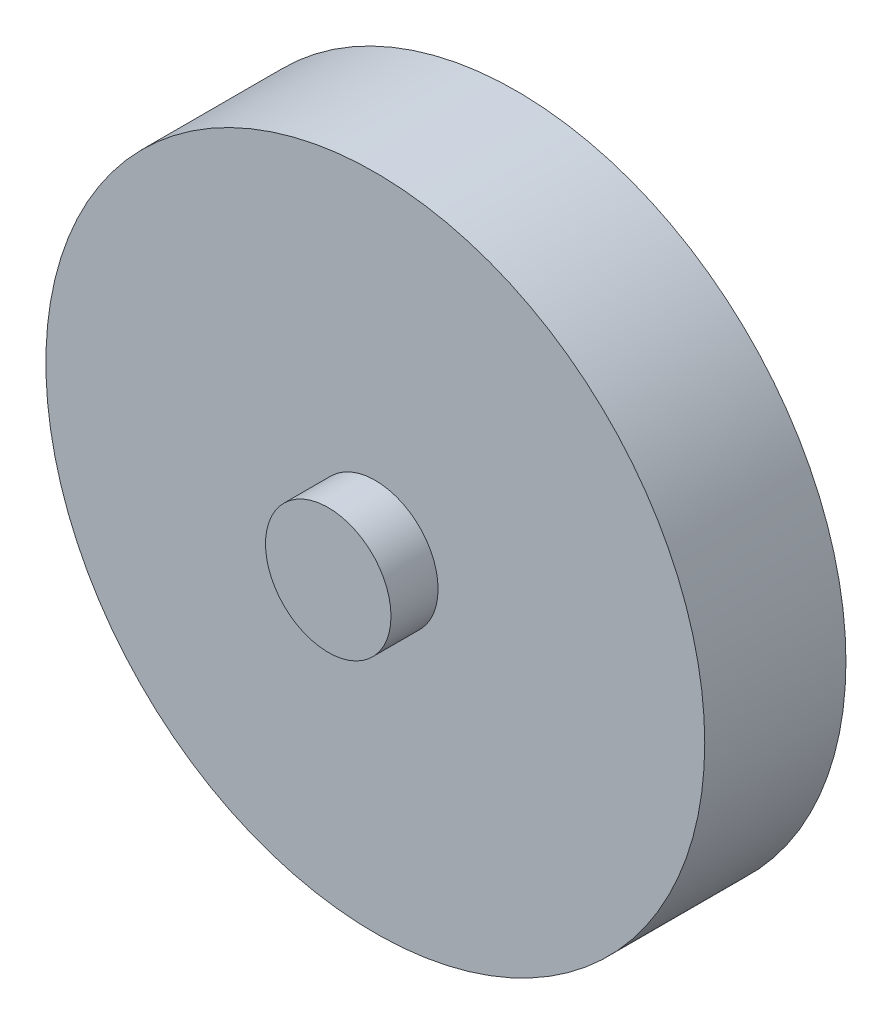
SolidWorks part; units mm, degrees
ref_plane "前视基准面" through (0, 0, 0) normal (0, 0, 1) x (1, 0, 0)
ref_plane "上视基准面" through (0, 0, 0) normal (0, 1, 0) x (1, 0, 0)
ref_plane "右视基准面" through (0, 0, 0) normal (1, 0, 0) x (0, 0, -1)
other "Configuration Table"
sketch "草图1" plane through (0, 0, 0) normal (0, 0, 1) x (1, 0, 0)
  circle A0 centre (0, 0) radius 8
extrude "凸台-拉伸1" add sketch "草图1" along normal blind 24
sketch "草图2" plane through (0, 0, 0) normal (0, 0, 1) x (1, 0, 0)
  circle A0 centre (0, 0) radius 42
extrude "凸台-拉伸2" add sketch "草图2" along normal blind 18
sketch "草图3" plane through (0, 0, 18) normal (0, 0, 1) x (1, 0, 0)
  line L0 (37.3016, 3.8521) -> (37.3889, 3.8612)
  line L1 (37.3889, 3.8612) -> (37.4611, 3.8717)
  line L2 (37.4611, 3.8717) -> (37.6757, 3.9151)
  line L3 (37.6757, 3.9151) -> (38.0282, 4.0092)
  line L4 (38.0282, 4.0092) -> (38.5127, 4.1711)
  line L5 (38.5127, 4.1711) -> (39.1215, 4.4175)
  line L6 (39.1215, 4.4175) -> (39.8456, 4.7642)
  line L7 (39.8456, 4.7642) -> (40.6741, 4.7642)
  line L8 (40.6741, 4.7642) -> (41.5951, 5.8179)
  line L9 (41.5951, 5.8179) -> (41.5951, 4.7642)
  line L10 (41.5951, 4.7642) -> (41.8082, 4.0092)
  line L11 (41.8082, 4.0092) -> (41.951, 2.0289)
  line L12 (41.951, 2.0289) -> (42, 0)
  line L13 (42, 0) -> (40.6741, 1.2633)
  line L14 (40.6741, 1.2633) -> (40.1003, 1.5277)
  line L15 (40.1003, 1.5277) -> (39.3309, 1.7569)
  line L16 (39.3309, 1.7569) -> (38.6911, 1.905)
  line L17 (38.6911, 1.905) -> (38.1872, 1.9891)
  line L18 (38.1872, 1.9891) -> (37.8243, 2.0269)
  line L19 (37.8243, 2.0269) -> (37.6055, 2.0362)
  line L20 (37.6055, 2.0362) -> (37.5326, 2.0353)
  line L21 (37.5326, 2.0353) -> (37.445, 2.0305)
  line L22 (37.445, 2.0305) -> (37.4175, 2.4866)
  line L23 (37.4175, 2.4866) -> (37.3844, 2.9422)
  line L24 (37.3844, 2.9422) -> (37.3458, 3.3974)
  line L25 (37.3458, 3.3974) -> (37.3016, 3.8521)
  line L26 (36.2398, 9.64) -> (36.3245, 9.6625)
  line L27 (36.3245, 9.6625) -> (36.3942, 9.6842)
  line L28 (36.3942, 9.6842) -> (36.5993, 9.7607)
  line L29 (36.5993, 9.7607) -> (36.9328, 9.9088)
  line L30 (36.9328, 9.9088) -> (37.386, 10.1445)
  line L31 (37.386, 10.1445) -> (37.9488, 10.483)
  line L32 (37.9488, 10.483) -> (38.6097, 10.9387)
  line L33 (38.6097, 10.9387) -> (39.3558, 11.5248)
  line L34 (39.3558, 11.5248) -> (39.8456, 11.5248)
  line L35 (39.8456, 11.5248) -> (40.5247, 11.034)
  line L36 (40.5247, 11.034) -> (40.5247, 10.483)
  line L37 (40.5247, 10.483) -> (41.1171, 8.5665)
  line L38 (41.1171, 8.5665) -> (41.3571, 7.3204)
  line L39 (41.3571, 7.3204) -> (39.8456, 7.3204)
  line L40 (39.8456, 7.3204) -> (39.3676, 7.782)
  line L41 (39.3676, 7.782) -> (37.9488, 7.782)
  line L42 (37.9488, 7.782) -> (37.9167, 7.9341)
  line L43 (37.9167, 7.9341) -> (37.4059, 7.9384)
  line L44 (37.4059, 7.9384) -> (37.0415, 7.9189)
  line L45 (37.0415, 7.9189) -> (36.824, 7.8939)
  line L46 (36.824, 7.8939) -> (36.7521, 7.8816)
  line L47 (36.7521, 7.8816) -> (36.6663, 7.8632)
  line L48 (36.6663, 7.8632) -> (36.5678, 8.3093)
  line L49 (36.5678, 8.3093) -> (36.4639, 8.7542)
  line L50 (36.4639, 8.7542) -> (36.2398, 9.64)
  line L51 (34.2856, 15.1904) -> (34.3658, 15.226)
  line L52 (34.3658, 15.226) -> (34.4312, 15.2583)
  line L53 (34.4312, 15.2583) -> (34.6218, 15.3659)
  line L54 (34.6218, 15.3659) -> (34.9281, 15.5643)
  line L55 (34.9281, 15.5643) -> (35.3388, 15.868)
  line L56 (35.3388, 15.868) -> (35.8417, 16.2905)
  line L57 (35.8417, 16.2905) -> (36.4232, 16.8439)
  line L58 (36.4232, 16.8439) -> (37.0683, 17.5395)
  line L59 (37.0683, 17.5395) -> (37.7615, 18.3868)
  line L60 (37.7615, 18.3868) -> (37.7615, 17.5395)
  line L61 (37.7615, 17.5395) -> (38.8029, 16.0727)
  line L62 (38.8029, 16.0727) -> (39.0096, 15.5643)
  line L63 (39.0096, 15.5643) -> (39.7028, 13.7)
  line L64 (39.7028, 13.7) -> (39.0096, 13.7)
  line L65 (39.0096, 13.7) -> (37.9488, 13.7)
  line L66 (37.9488, 13.7) -> (36.4232, 13.7)
  line L67 (36.4232, 13.7) -> (36.2087, 13.7679)
  line L68 (36.2087, 13.7679) -> (35.7035, 13.6922)
  line L69 (35.7035, 13.6922) -> (35.3467, 13.616)
  line L70 (35.3467, 13.616) -> (35.1358, 13.5573)
  line L71 (35.1358, 13.5573) -> (35.0666, 13.5339)
  line L72 (35.0666, 13.5339) -> (34.9848, 13.5023)
  line L73 (34.9848, 13.5023) -> (34.8177, 13.9275)
  line L74 (34.8177, 13.9275) -> (34.6455, 14.3506)
  line L75 (34.6455, 14.3506) -> (34.4681, 14.7716)
  line L76 (34.4681, 14.7716) -> (34.2856, 15.1904)
  line L77 (31.4872, 20.3669) -> (31.5608, 20.4145)
  line L78 (31.5608, 20.4145) -> (31.6204, 20.4566)
  line L79 (31.6204, 20.4566) -> (31.7918, 20.5928)
  line L80 (31.7918, 20.5928) -> (32.0632, 20.8367)
  line L81 (32.0632, 20.8367) -> (32.4214, 21.2009)
  line L82 (32.4214, 21.2009) -> (32.8521, 21.6968)
  line L83 (32.8521, 21.6968) -> (33.3398, 22.3344)
  line L84 (33.3398, 22.3344) -> (33.3398, 23.1223)
  line L85 (33.3398, 23.1223) -> (34.4202, 24.0676)
  line L86 (34.4202, 24.0676) -> (34.4202, 22.3344)
  line L87 (34.4202, 22.3344) -> (36.4232, 22.3344)
  line L88 (36.4232, 22.3344) -> (36.4232, 20.913)
  line L89 (36.4232, 20.913) -> (37.0708, 19.7422)
  line L90 (37.0708, 19.7422) -> (36.4232, 19.7422)
  line L91 (36.4232, 19.7422) -> (34.4202, 19.7422)
  line L92 (34.4202, 19.7422) -> (34.2465, 19.4213)
  line L93 (34.2465, 19.4213) -> (33.6091, 19.2627)
  line L94 (33.6091, 19.2627) -> (33.122, 19.1089)
  line L95 (33.122, 19.1089) -> (32.7815, 18.9778)
  line L96 (32.7815, 18.9778) -> (32.5824, 18.8868)
  line L97 (32.5824, 18.8868) -> (32.5178, 18.8529)
  line L98 (32.5178, 18.8529) -> (32.4419, 18.8089)
  line L99 (32.4419, 18.8089) -> (32.2103, 19.2027)
  line L100 (32.2103, 19.2027) -> (31.974, 19.5937)
  line L101 (31.974, 19.5937) -> (31.4872, 20.3669)
  line L102 (27.9134, 25.0418) -> (27.9787, 25.1004)
  line L103 (27.9787, 25.1004) -> (28.0309, 25.1513)
  line L104 (28.0309, 25.1513) -> (28.179, 25.3126)
  line L105 (28.179, 25.3126) -> (28.4089, 25.5959)
  line L106 (28.4089, 25.5959) -> (28.7057, 26.0117)
  line L107 (28.7057, 26.0117) -> (29.0535, 26.5689)
  line L108 (29.0535, 26.5689) -> (29.4354, 27.2749)
  line L109 (29.4354, 27.2749) -> (29.4354, 28.1358)
  line L110 (29.4354, 28.1358) -> (30.2315, 29.1558)
  line L111 (30.2315, 29.1558) -> (31.183, 28.1358)
  line L112 (31.183, 28.1358) -> (31.9387, 27.2749)
  line L113 (31.9387, 27.2749) -> (32.5284, 26.5689)
  line L114 (32.5284, 26.5689) -> (33.3398, 25.5433)
  line L115 (33.3398, 25.5433) -> (32.5284, 25.5433)
  line L116 (32.5284, 25.5433) -> (31.9387, 25.5433)
  line L117 (31.9387, 25.5433) -> (31.183, 25.3126)
  line L118 (31.183, 25.3126) -> (29.4354, 25.0418)
  line L119 (29.4354, 25.0418) -> (29.4354, 24.0676)
  line L120 (29.4354, 24.0676) -> (29.4091, 23.8723)
  line L121 (29.4091, 23.8723) -> (29.2267, 23.7513)
  line L122 (29.2267, 23.7513) -> (29.1682, 23.7077)
  line L123 (29.1682, 23.7077) -> (29.1001, 23.6524)
  line L124 (29.1001, 23.6524) -> (28.8098, 24.0051)
  line L125 (28.8098, 24.0051) -> (28.5152, 24.3543)
  line L126 (28.5152, 24.3543) -> (28.2164, 24.6999)
  line L127 (28.2164, 24.6999) -> (27.9134, 25.0418)
  line L128 (23.6524, 29.1558) -> (23.7077, 29.1558)
  line L129 (23.7077, 29.1558) -> (23.7513, 29.2267)
  line L130 (23.7513, 29.2267) -> (23.8723, 29.4091)
  line L131 (23.8723, 29.4091) -> (24.0551, 29.7249)
  line L132 (24.0551, 29.7249) -> (24.2832, 30.182)
  line L133 (24.2832, 30.182) -> (24.5395, 30.7867)
  line L134 (24.5395, 30.7867) -> (24.8063, 31.5438)
  line L135 (24.8063, 31.5438) -> (24.8063, 32.4565)
  line L136 (24.8063, 32.4565) -> (24.8063, 33.8917)
  line L137 (24.8063, 33.8917) -> (26.1255, 32.5725)
  line L138 (26.1255, 32.5725) -> (27.2768, 31.9371)
  line L139 (27.2768, 31.9371) -> (28.7057, 30.6591)
  line L140 (28.7057, 30.6591) -> (29.1558, 30.2315)
  line L141 (29.1558, 30.2315) -> (28.7057, 30.2315)
  line L142 (28.7057, 30.2315) -> (27.2768, 28.8026)
  line L143 (27.2768, 28.8026) -> (26.5689, 29.0535)
  line L144 (26.5689, 29.0535) -> (26.0117, 28.7057)
  line L145 (26.0117, 28.7057) -> (25.5959, 28.4089)
  line L146 (25.5959, 28.4089) -> (25.3126, 28.179)
  line L147 (25.3126, 28.179) -> (25.1513, 28.0309)
  line L148 (25.1513, 28.0309) -> (25.1004, 27.9787)
  line L149 (25.1004, 27.9787) -> (25.0418, 27.9134)
  line L150 (25.0418, 27.9134) -> (24.6999, 28.2164)
  line L151 (24.6999, 28.2164) -> (24.3543, 28.5152)
  line L152 (24.3543, 28.5152) -> (23.7077, 29.1558)
  line L153 (23.7077, 29.1558) -> (23.6524, 29.1558)
  line L154 (18.8089, 32.4565) -> (18.8529, 32.4565)
  line L155 (18.8529, 32.4565) -> (18.8868, 32.5824)
  line L156 (18.8868, 32.5824) -> (18.9778, 32.7815)
  line L157 (18.9778, 32.7815) -> (19.1089, 33.122)
  line L158 (19.1089, 33.122) -> (19.2627, 33.6091)
  line L159 (19.2627, 33.6091) -> (19.4213, 34.2465)
  line L160 (19.4213, 34.2465) -> (19.4213, 35.036)
  line L161 (19.4213, 35.036) -> (19.4213, 35.978)
  line L162 (19.4213, 35.978) -> (19.4213, 37.24)
  line L163 (19.4213, 37.24) -> (20.6833, 35.978)
  line L164 (20.6833, 35.978) -> (21.6699, 35.978)
  line L165 (21.6699, 35.978) -> (23.7513, 35.036)
  line L166 (23.7513, 35.036) -> (24.0676, 34.4202)
  line L167 (24.0676, 34.4202) -> (23.7513, 34.4202)
  line L168 (23.7513, 34.4202) -> (22.5026, 33.1715)
  line L169 (22.5026, 33.1715) -> (21.6699, 33.1715)
  line L170 (21.6699, 33.1715) -> (21.2009, 32.4214)
  line L171 (21.2009, 32.4214) -> (20.8367, 32.0632)
  line L172 (20.8367, 32.0632) -> (20.5928, 31.7918)
  line L173 (20.5928, 31.7918) -> (20.4566, 31.6204)
  line L174 (20.4566, 31.6204) -> (20.4145, 31.5608)
  line L175 (20.4145, 31.5608) -> (20.3669, 31.4872)
  line L176 (20.3669, 31.4872) -> (19.9818, 31.7329)
  line L177 (19.9818, 31.7329) -> (19.5937, 31.974)
  line L178 (19.5937, 31.974) -> (18.8529, 32.4565)
  line L179 (18.8529, 32.4565) -> (18.8089, 32.4565)
  line L180 (13.5023, 34.2465) -> (13.5339, 35.036)
  line L181 (13.5339, 35.036) -> (13.5573, 35.1358)
  line L182 (13.5573, 35.1358) -> (13.616, 35.3467)
  line L183 (13.616, 35.3467) -> (13.6922, 35.7035)
  line L184 (13.6922, 35.7035) -> (13.7679, 36.2087)
  line L185 (13.7679, 36.2087) -> (13.8248, 36.863)
  line L186 (13.8248, 36.863) -> (13.8248, 37.24)
  line L187 (13.8248, 37.24) -> (13.8248, 38.6136)
  line L188 (13.8248, 38.6136) -> (13.8248, 39.6595)
  line L189 (13.8248, 39.6595) -> (14.8931, 39.2708)
  line L190 (14.8931, 39.2708) -> (16.0727, 39.2708)
  line L191 (16.0727, 39.2708) -> (17.2376, 38.2997)
  line L192 (17.2376, 38.2997) -> (18.3868, 37.7615)
  line L193 (18.3868, 37.7615) -> (17.2376, 37.7615)
  line L194 (17.2376, 37.7615) -> (17.2376, 35.978)
  line L195 (17.2376, 35.978) -> (16.0727, 35.978)
  line L196 (16.0727, 35.978) -> (15.868, 35.3388)
  line L197 (15.868, 35.3388) -> (15.5643, 34.9281)
  line L198 (15.5643, 34.9281) -> (15.3659, 34.6218)
  line L199 (15.3659, 34.6218) -> (15.2583, 34.4312)
  line L200 (15.2583, 34.4312) -> (15.226, 34.3658)
  line L201 (15.226, 34.3658) -> (15.1904, 34.2856)
  line L202 (15.1904, 34.2856) -> (14.7716, 34.4681)
  line L203 (14.7716, 34.4681) -> (14.3506, 34.6455)
  line L204 (14.3506, 34.6455) -> (13.5339, 35.036)
  line L205 (13.5339, 35.036) -> (13.5023, 34.9848)
  line L206 (7.8632, 36.2087) -> (7.8816, 36.2087)
  line L207 (7.8816, 36.2087) -> (7.8939, 36.824)
  line L208 (7.8939, 36.824) -> (7.9189, 37.0415)
  line L209 (7.9189, 37.0415) -> (7.9384, 37.4059)
  line L210 (7.9384, 37.4059) -> (7.9341, 37.9167)
  line L211 (7.9341, 37.9167) -> (7.888, 38.5719)
  line L212 (7.888, 38.5719) -> (7.888, 38.6136)
  line L213 (7.888, 38.6136) -> (7.888, 39.6595)
  line L214 (7.888, 39.6595) -> (7.888, 41.2526)
  line L215 (7.888, 41.2526) -> (8.5665, 41.1171)
  line L216 (8.5665, 41.1171) -> (9.8047, 41.1171)
  line L217 (9.8047, 41.1171) -> (11.034, 41.1171)
  line L218 (11.034, 41.1171) -> (12.2532, 40.1729)
  line L219 (12.2532, 40.1729) -> (12.2532, 38.6136)
  line L220 (12.2532, 38.6136) -> (11.034, 38.6136)
  line L221 (11.034, 38.6136) -> (10.483, 37.9488)
  line L222 (10.483, 37.9488) -> (10.1445, 37.386)
  line L223 (10.1445, 37.386) -> (9.9088, 36.9328)
  line L224 (9.9088, 36.9328) -> (9.7607, 36.5993)
  line L225 (9.7607, 36.5993) -> (9.6842, 36.3942)
  line L226 (9.6842, 36.3942) -> (9.6625, 36.3245)
  line L227 (9.6625, 36.3245) -> (9.64, 36.2398)
  line L228 (9.64, 36.2398) -> (9.1978, 36.3545)
  line L229 (9.1978, 36.3545) -> (8.7542, 36.4639)
  line L230 (8.7542, 36.4639) -> (8.3093, 36.5678)
  line L231 (8.3093, 36.5678) -> (7.8939, 36.824)
  line L232 (2.0305, 36.824) -> (2.0353, 36.824)
  line L233 (2.0353, 36.824) -> (2.0305, 37.0415)
  line L234 (2.0305, 37.0415) -> (2.0305, 38.5719)
  line L235 (2.0305, 38.5719) -> (1.9891, 38.1872)
  line L236 (1.9891, 38.1872) -> (2.0305, 38.5719)
  line L237 (2.0305, 38.5719) -> (1.7569, 39.3309)
  line L238 (1.7569, 39.3309) -> (1.5277, 40.1003)
  line L239 (1.5277, 40.1003) -> (1.5277, 41.2526)
  line L240 (1.5277, 41.2526) -> (2.0289, 41.951)
  line L241 (2.0289, 41.951) -> (3.2953, 41.8705)
  line L242 (3.2953, 41.8705) -> (4.5587, 41.8705)
  line L243 (4.5587, 41.8705) -> (5.8179, 41.8705)
  line L244 (5.8179, 41.8705) -> (4.5587, 41.2526)
  line L245 (4.5587, 41.2526) -> (4.5587, 39.3309)
  line L246 (4.5587, 39.3309) -> (4.4175, 39.1215)
  line L247 (4.4175, 39.1215) -> (4.1711, 38.5127)
  line L248 (4.1711, 38.5127) -> (4.0092, 38.0282)
  line L249 (4.0092, 38.0282) -> (3.9151, 37.6757)
  line L250 (3.9151, 37.6757) -> (3.8717, 37.4611)
  line L251 (3.8717, 37.4611) -> (3.8612, 37.3889)
  line L252 (3.8612, 37.3889) -> (3.8521, 37.3016)
  line L253 (3.8521, 37.3016) -> (3.3974, 37.3458)
  line L254 (3.3974, 37.3458) -> (2.9422, 37.3844)
  line L255 (2.9422, 37.3844) -> (2.4866, 37.4175)
  line L256 (2.4866, 37.4175) -> (2.0305, 37.0415)
  line L257 (-3.8521, 36.824) -> (-3.8612, 36.824)
  line L258 (-3.8612, 36.824) -> (-3.8717, 37.4611)
  line L259 (-3.8717, 37.4611) -> (-3.9151, 37.6757)
  line L260 (-3.9151, 37.6757) -> (-4.0092, 38.0282)
  line L261 (-4.0092, 38.0282) -> (-4.1711, 38.5127)
  line L262 (-4.1711, 38.5127) -> (-4.4175, 39.1215)
  line L263 (-4.4175, 39.1215) -> (-4.7642, 39.8456)
  line L264 (-4.7642, 39.8456) -> (-4.7642, 40.1003)
  line L265 (-4.7642, 40.1003) -> (-6.2033, 41.5394)
  line L266 (-6.2033, 41.5394) -> (-4.7642, 41.5394)
  line L267 (-4.7642, 41.5394) -> (-4.0092, 41.5394)
  line L268 (-4.0092, 41.5394) -> (-2.0289, 41.951)
  line L269 (-2.0289, 41.951) -> (0, 41.951)
  line L270 (0, 41.951) -> (-1.2009, 41.7452)
  line L271 (-1.2009, 41.7452) -> (-1.2009, 40.1003)
  line L272 (-1.2009, 40.1003) -> (-1.7569, 39.3309)
  line L273 (-1.7569, 39.3309) -> (-1.905, 38.6911)
  line L274 (-1.905, 38.6911) -> (-1.9891, 38.1872)
  line L275 (-1.9891, 38.1872) -> (-2.0269, 37.8243)
  line L276 (-2.0269, 37.8243) -> (-2.0362, 37.6055)
  line L277 (-2.0362, 37.6055) -> (-2.0353, 37.5326)
  line L278 (-2.0353, 37.5326) -> (-2.0305, 37.445)
  line L279 (-2.0305, 37.445) -> (-2.4866, 37.4175)
  line L280 (-2.4866, 37.4175) -> (-2.9422, 37.3844)
  line L281 (-2.9422, 37.3844) -> (-3.3974, 37.3458)
  line L282 (-3.3974, 37.3458) -> (-3.8717, 37.4611)
  line L283 (-9.64, 36.824) -> (-9.6625, 36.824)
  line L284 (-9.6625, 36.824) -> (-9.6842, 36.3942)
  line L285 (-9.6842, 36.3942) -> (-9.7607, 36.5993)
  line L286 (-9.7607, 36.5993) -> (-9.6625, 36.824)
  line L287 (-9.6625, 36.824) -> (-10.1445, 37.386)
  line L288 (-10.1445, 37.386) -> (-10.483, 37.9488)
  line L289 (-10.483, 37.9488) -> (-10.9387, 38.6097)
  line L290 (-10.9387, 38.6097) -> (-11.5248, 39.3558)
  line L291 (-11.5248, 39.3558) -> (-11.5248, 40.3879)
  line L292 (-11.5248, 40.3879) -> (-11.034, 40.5247)
  line L293 (-11.034, 40.5247) -> (-10.483, 40.5247)
  line L294 (-10.483, 40.5247) -> (-8.5665, 40.5247)
  line L295 (-8.5665, 40.5247) -> (-7.3204, 41.3571)
  line L296 (-7.3204, 41.3571) -> (-7.9435, 40.9409)
  line L297 (-7.9435, 40.9409) -> (-7.9435, 39.8456)
  line L298 (-7.9435, 39.8456) -> (-7.9435, 37.9488)
  line L299 (-7.9435, 37.9488) -> (-7.9341, 37.9167)
  line L300 (-7.9341, 37.9167) -> (-7.9384, 37.4059)
  line L301 (-7.9384, 37.4059) -> (-7.9189, 37.0415)
  line L302 (-7.9189, 37.0415) -> (-7.8939, 36.824)
  line L303 (-7.8939, 36.824) -> (-7.8816, 36.7521)
  line L304 (-7.8816, 36.7521) -> (-7.8632, 36.6663)
  line L305 (-7.8632, 36.6663) -> (-8.3093, 36.5678)
  line L306 (-8.3093, 36.5678) -> (-8.7542, 36.4639)
  line L307 (-8.7542, 36.4639) -> (-9.1978, 36.3545)
  line L308 (-9.1978, 36.3545) -> (-9.6842, 36.3942)
  line L309 (-15.1904, 34.2465) -> (-15.226, 34.2465)
  line L310 (-15.226, 34.2465) -> (-15.2583, 34.4312)
  line L311 (-15.2583, 34.4312) -> (-15.3659, 34.6218)
  line L312 (-15.3659, 34.6218) -> (-15.5643, 34.9281)
  line L313 (-15.5643, 34.9281) -> (-15.868, 35.3388)
  line L314 (-15.868, 35.3388) -> (-16.2905, 35.8417)
  line L315 (-16.2905, 35.8417) -> (-16.8439, 36.4232)
  line L316 (-16.8439, 36.4232) -> (-17.5395, 37.0683)
  line L317 (-17.5395, 37.0683) -> (-18.3868, 37.7615)
  line L318 (-18.3868, 37.7615) -> (-17.5395, 37.7615)
  line L319 (-17.5395, 37.7615) -> (-15.9452, 39.3558)
  line L320 (-15.9452, 39.3558) -> (-15.5643, 39.3558)
  line L321 (-15.5643, 39.3558) -> (-13.7, 39.3558)
  line L322 (-13.7, 39.3558) -> (-13.809, 38.6136)
  line L323 (-13.809, 38.6136) -> (-13.809, 37.9488)
  line L324 (-13.809, 37.9488) -> (-13.809, 36.4232)
  line L325 (-13.809, 36.4232) -> (-13.7679, 36.2087)
  line L326 (-13.7679, 36.2087) -> (-13.6922, 35.7035)
  line L327 (-13.6922, 35.7035) -> (-13.616, 35.3467)
  line L328 (-13.616, 35.3467) -> (-13.5573, 35.1358)
  line L329 (-13.5573, 35.1358) -> (-13.5339, 35.0666)
  line L330 (-13.5339, 35.0666) -> (-13.5023, 34.9848)
  line L331 (-13.5023, 34.9848) -> (-13.9275, 34.8177)
  line L332 (-13.9275, 34.8177) -> (-14.3506, 34.6455)
  line L333 (-14.3506, 34.6455) -> (-14.7716, 34.4681)
  line L334 (-14.7716, 34.4681) -> (-15.1904, 34.2465)
  line L335 (-20.3669, 31.974) -> (-20.4145, 31.974)
  line L336 (-20.4145, 31.974) -> (-20.4566, 31.6204)
  line L337 (-20.4566, 31.6204) -> (-20.5928, 31.7918)
  line L338 (-20.5928, 31.7918) -> (-20.8367, 32.0632)
  line L339 (-20.8367, 32.0632) -> (-21.2009, 32.4214)
  line L340 (-21.2009, 32.4214) -> (-21.6968, 32.8521)
  line L341 (-21.6968, 32.8521) -> (-22.3344, 33.3398)
  line L342 (-22.3344, 33.3398) -> (-23.1223, 33.3398)
  line L343 (-23.1223, 33.3398) -> (-24.0676, 34.4202)
  line L344 (-24.0676, 34.4202) -> (-23.1223, 34.4202)
  line L345 (-23.1223, 34.4202) -> (-21.4082, 36.1343)
  line L346 (-21.4082, 36.1343) -> (-20.8531, 36.4575)
  line L347 (-20.8531, 36.4575) -> (-20.4145, 36.4575)
  line L348 (-20.4145, 36.4575) -> (-19.6795, 35.978)
  line L349 (-19.6795, 35.978) -> (-19.6795, 34.4202)
  line L350 (-19.6795, 34.4202) -> (-19.4213, 34.2465)
  line L351 (-19.4213, 34.2465) -> (-19.2627, 33.6091)
  line L352 (-19.2627, 33.6091) -> (-19.1089, 33.122)
  line L353 (-19.1089, 33.122) -> (-18.9778, 32.7815)
  line L354 (-18.9778, 32.7815) -> (-18.8868, 32.5824)
  line L355 (-18.8868, 32.5824) -> (-18.8529, 32.5178)
  line L356 (-18.8529, 32.5178) -> (-18.8089, 32.4419)
  line L357 (-18.8089, 32.4419) -> (-19.2027, 32.2103)
  line L358 (-19.2027, 32.2103) -> (-19.5937, 31.974)
  line L359 (-19.5937, 31.974) -> (-20.3669, 31.974)
  line L360 (-20.3669, 31.974) -> (-20.4566, 31.6204)
  line L361 (-25.0418, 28.5152) -> (-25.1004, 28.5152)
  line L362 (-25.1004, 28.5152) -> (-25.1513, 28.0309)
  line L363 (-25.1513, 28.0309) -> (-25.3126, 28.179)
  line L364 (-25.3126, 28.179) -> (-25.5959, 28.4089)
  line L365 (-25.5959, 28.4089) -> (-26.0117, 28.7057)
  line L366 (-26.0117, 28.7057) -> (-26.5689, 29.0535)
  line L367 (-26.5689, 29.0535) -> (-27.2749, 29.4354)
  line L368 (-27.2749, 29.4354) -> (-28.1358, 29.4354)
  line L369 (-28.1358, 29.4354) -> (-29.672, 29.7249)
  line L370 (-29.672, 29.7249) -> (-28.6995, 30.665)
  line L371 (-28.6995, 30.665) -> (-27.2749, 31.9387)
  line L372 (-27.2749, 31.9387) -> (-26.5689, 32.5284)
  line L373 (-26.5689, 32.5284) -> (-25.5974, 33.3398)
  line L374 (-25.5974, 33.3398) -> (-25.5974, 32.5284)
  line L375 (-25.5974, 32.5284) -> (-24.0676, 31.9387)
  line L376 (-24.0676, 31.9387) -> (-24.0676, 30.665)
  line L377 (-24.0676, 30.665) -> (-24.2832, 30.182)
  line L378 (-24.2832, 30.182) -> (-24.0551, 29.7249)
  line L379 (-24.0551, 29.7249) -> (-23.8723, 29.4091)
  line L380 (-23.8723, 29.4091) -> (-23.7513, 29.2267)
  line L381 (-23.7513, 29.2267) -> (-23.7077, 29.1682)
  line L382 (-23.7077, 29.1682) -> (-23.6524, 29.1001)
  line L383 (-23.6524, 29.1001) -> (-24.0051, 28.8098)
  line L384 (-24.0051, 28.8098) -> (-24.3543, 28.5152)
  line L385 (-24.3543, 28.5152) -> (-25.0418, 28.5152)
  line L386 (-25.0418, 28.5152) -> (-25.1513, 28.0309)
  line L387 (-29.672, 24.3543) -> (-29.672, 24.6999)
  line L388 (-29.672, 24.3543) -> (-30.182, 24.2832)
  line L389 (-30.182, 24.2832) -> (-30.7867, 24.5395)
  line L390 (-30.7867, 24.5395) -> (-31.5438, 24.8063)
  line L391 (-31.5438, 24.8063) -> (-32.4565, 24.8063)
  line L392 (-32.4565, 24.8063) -> (-33.8917, 24.8063)
  line L393 (-33.8917, 24.8063) -> (-33.1741, 25.7581)
  line L394 (-33.1741, 25.7581) -> (-31.9371, 27.2768)
  line L395 (-31.9371, 27.2768) -> (-31.5438, 27.7306)
  line L396 (-31.5438, 27.7306) -> (-29.672, 29.7249)
  line L397 (-29.672, 29.7249) -> (-29.672, 27.7306)
  line L398 (-29.672, 27.7306) -> (-29.4354, 27.2749)
  line L399 (-29.4354, 27.2749) -> (-29.0535, 26.5689)
  line L400 (-29.0535, 26.5689) -> (-28.7057, 26.0117)
  line L401 (-28.7057, 26.0117) -> (-28.4089, 25.5959)
  line L402 (-28.4089, 25.5959) -> (-28.179, 25.3126)
  line L403 (-28.179, 25.3126) -> (-28.0309, 25.1513)
  line L404 (-28.0309, 25.1513) -> (-27.9787, 25.1004)
  line L405 (-27.9787, 25.1004) -> (-27.9134, 25.0418)
  line L406 (-27.9134, 25.0418) -> (-28.2164, 24.6999)
  line L407 (-28.2164, 24.6999) -> (-28.5152, 24.3543)
  line L408 (-28.5152, 24.3543) -> (-28.8098, 24.0051)
  line L409 (-28.8098, 24.0051) -> (-29.1001, 23.6524)
  line L410 (-32.4565, 19.2027) -> (-32.4565, 19.5937)
  line L411 (-32.4565, 19.2027) -> (-32.5824, 18.8868)
  line L412 (-32.5824, 18.8868) -> (-32.7815, 18.9778)
  line L413 (-32.7815, 18.9778) -> (-33.122, 19.1089)
  line L414 (-33.122, 19.1089) -> (-33.6091, 19.2627)
  line L415 (-33.6091, 19.2627) -> (-34.2465, 19.4213)
  line L416 (-34.2465, 19.4213) -> (-35.036, 19.4213)
  line L417 (-35.036, 19.4213) -> (-35.978, 19.4213)
  line L418 (-35.978, 19.4213) -> (-37.24, 19.4213)
  line L419 (-37.24, 19.4213) -> (-36.7313, 20.3669)
  line L420 (-36.7313, 20.3669) -> (-35.978, 21.6699)
  line L421 (-35.978, 21.6699) -> (-35.036, 23.1619)
  line L422 (-35.036, 23.1619) -> (-33.8917, 24.8063)
  line L423 (-33.8917, 24.8063) -> (-33.8917, 23.1619)
  line L424 (-33.8917, 23.1619) -> (-33.8917, 21.6699)
  line L425 (-33.8917, 21.6699) -> (-32.4565, 21.6699)
  line L426 (-32.4565, 21.6699) -> (-32.4214, 21.2009)
  line L427 (-32.4214, 21.2009) -> (-32.0632, 20.8367)
  line L428 (-32.0632, 20.8367) -> (-31.7918, 20.5928)
  line L429 (-31.7918, 20.5928) -> (-31.6204, 20.4566)
  line L430 (-31.6204, 20.4566) -> (-31.5608, 20.4145)
  line L431 (-31.5608, 20.4145) -> (-31.4872, 20.3669)
  line L432 (-31.4872, 20.3669) -> (-31.7329, 19.9818)
  line L433 (-31.7329, 19.9818) -> (-31.974, 19.5937)
  line L434 (-31.974, 19.5937) -> (-32.4565, 19.2027)
  line L435 (-32.4565, 19.2027) -> (-32.5824, 18.8868)
  line L436 (-35.036, 13.9275) -> (-35.978, 14.3506)
  line L437 (-35.036, 13.9275) -> (-35.7035, 13.6922)
  line L438 (-35.7035, 13.6922) -> (-36.2087, 13.7679)
  line L439 (-36.2087, 13.7679) -> (-36.863, 13.8248)
  line L440 (-36.863, 13.8248) -> (-37.24, 13.8248)
  line L441 (-37.24, 13.8248) -> (-38.6136, 13.8248)
  line L442 (-38.6136, 13.8248) -> (-39.6595, 13.8248)
  line L443 (-39.6595, 13.8248) -> (-39.4723, 14.3506)
  line L444 (-39.4723, 14.3506) -> (-39.0882, 15.3659)
  line L445 (-39.0882, 15.3659) -> (-38.4744, 16.8439)
  line L446 (-38.4744, 16.8439) -> (-37.7615, 18.3868)
  line L447 (-37.7615, 18.3868) -> (-37.7615, 16.8439)
  line L448 (-37.7615, 16.8439) -> (-35.978, 16.8439)
  line L449 (-35.978, 16.8439) -> (-35.8417, 16.2905)
  line L450 (-35.8417, 16.2905) -> (-35.3388, 15.868)
  line L451 (-35.3388, 15.868) -> (-34.9281, 15.5643)
  line L452 (-34.9281, 15.5643) -> (-34.6218, 15.3659)
  line L453 (-34.6218, 15.3659) -> (-34.4312, 15.2583)
  line L454 (-34.4312, 15.2583) -> (-34.3658, 15.226)
  line L455 (-34.3658, 15.226) -> (-34.2856, 15.1904)
  line L456 (-34.2856, 15.1904) -> (-34.4681, 14.7716)
  line L457 (-34.4681, 14.7716) -> (-34.6455, 14.3506)
  line L458 (-34.6455, 14.3506) -> (-35.036, 13.9275)
  line L459 (-35.036, 13.9275) -> (-34.9848, 13.5023)
  line L460 (-36.2087, 8.3093) -> (-37.24, 8.3093)
  line L461 (-37.24, 8.3093) -> (-37.4059, 7.9384)
  line L462 (-37.4059, 7.9384) -> (-37.9167, 7.9341)
  line L463 (-37.9167, 7.9341) -> (-38.5719, 7.888)
  line L464 (-38.5719, 7.888) -> (-39.6595, 7.888)
  line L465 (-39.6595, 7.888) -> (-40.2984, 7.5985)
  line L466 (-40.2984, 7.5985) -> (-41.3069, 7.5985)
  line L467 (-41.3069, 7.5985) -> (-41.2526, 7.888)
  line L468 (-41.2526, 7.888) -> (-40.8787, 9.64)
  line L469 (-40.8787, 9.64) -> (-40.6707, 10.483)
  line L470 (-40.6707, 10.483) -> (-40.3879, 11.5248)
  line L471 (-40.3879, 11.5248) -> (-39.6595, 11.5248)
  line L472 (-39.6595, 11.5248) -> (-38.6136, 11.5248)
  line L473 (-38.6136, 11.5248) -> (-38.6136, 10.483)
  line L474 (-38.6136, 10.483) -> (-37.24, 10.483)
  line L475 (-37.24, 10.483) -> (-36.9328, 9.9088)
  line L476 (-36.9328, 9.9088) -> (-36.5993, 9.7607)
  line L477 (-36.5993, 9.7607) -> (-36.3942, 9.6842)
  line L478 (-36.3942, 9.6842) -> (-36.3245, 9.6625)
  line L479 (-36.3245, 9.6625) -> (-36.2398, 9.64)
  line L480 (-36.2398, 9.64) -> (-36.3545, 9.1978)
  line L481 (-36.3545, 9.1978) -> (-36.4639, 8.7542)
  line L482 (-36.4639, 8.7542) -> (-36.2087, 8.3093)
  line L483 (-36.2087, 8.3093) -> (-36.6663, 7.8632)
  line L484 (-37.9167, 2.4866) -> (-38.5719, 2.4866)
  line L485 (-37.9167, 2.4866) -> (-38.1872, 1.9891)
  line L486 (-38.1872, 1.9891) -> (-38.6911, 1.905)
  line L487 (-38.6911, 1.905) -> (-39.3309, 1.7569)
  line L488 (-39.3309, 1.7569) -> (-40.1003, 1.5277)
  line L489 (-40.1003, 1.5277) -> (-41.3069, 1.5277)
  line L490 (-41.3069, 1.5277) -> (-41.9931, 0.7606)
  line L491 (-41.9931, 0.7606) -> (-41.3069, 1.5277)
  line L492 (-41.3069, 1.5277) -> (-41.823, 3.8521)
  line L493 (-41.823, 3.8521) -> (-41.5951, 5.8179)
  line L494 (-41.5951, 5.8179) -> (-41.3069, 5.8179)
  line L495 (-41.3069, 5.8179) -> (-40.2984, 4.8093)
  line L496 (-40.2984, 4.8093) -> (-38.5719, 4.8093)
  line L497 (-38.5719, 4.8093) -> (-38.5127, 4.1711)
  line L498 (-38.5127, 4.1711) -> (-38.0282, 4.0092)
  line L499 (-38.0282, 4.0092) -> (-37.6757, 3.9151)
  line L500 (-37.6757, 3.9151) -> (-37.4611, 3.8717)
  line L501 (-37.4611, 3.8717) -> (-37.3889, 3.8612)
  line L502 (-37.3889, 3.8612) -> (-37.3016, 3.8521)
  line L503 (-37.3016, 3.8521) -> (-37.3458, 3.3974)
  line L504 (-37.3458, 3.3974) -> (-37.3844, 2.9422)
  line L505 (-37.3844, 2.9422) -> (-37.4175, 2.4866)
  line L506 (-37.4175, 2.4866) -> (-37.445, 2.0305)
  line L507 (-37.445, -3.8521) -> (-37.445, -3.8612)
  line L508 (-37.445, -3.8612) -> (-37.4611, -3.8717)
  line L509 (-37.4611, -3.8717) -> (-37.6757, -3.9151)
  line L510 (-37.6757, -3.9151) -> (-38.0282, -4.0092)
  line L511 (-38.0282, -4.0092) -> (-38.5127, -4.1711)
  line L512 (-38.5127, -4.1711) -> (-39.1215, -4.4175)
  line L513 (-39.1215, -4.4175) -> (-39.8456, -4.7642)
  line L514 (-39.8456, -4.7642) -> (-41.3069, -4.7642)
  line L515 (-41.3069, -4.7642) -> (-41.5951, -5.8179)
  line L516 (-41.5951, -5.8179) -> (-41.3069, -4.7642)
  line L517 (-41.3069, -4.7642) -> (-41.8221, -3.8611)
  line L518 (-41.8221, -3.8611) -> (-41.8221, -2.0289)
  line L519 (-41.8221, -2.0289) -> (-42, 0)
  line L520 (-42, 0) -> (-41.3069, -1.2009)
  line L521 (-41.3069, -1.2009) -> (-40.1003, -1.2009)
  line L522 (-40.1003, -1.2009) -> (-39.3309, -1.7569)
  line L523 (-39.3309, -1.7569) -> (-38.6911, -1.905)
  line L524 (-38.6911, -1.905) -> (-38.1872, -1.9891)
  line L525 (-38.1872, -1.9891) -> (-37.8243, -2.0269)
  line L526 (-37.8243, -2.0269) -> (-37.6055, -2.0362)
  line L527 (-37.6055, -2.0362) -> (-37.5326, -2.0353)
  line L528 (-37.5326, -2.0353) -> (-37.445, -2.0305)
  line L529 (-37.445, -2.0305) -> (-37.4175, -2.4866)
  line L530 (-37.4175, -2.4866) -> (-37.3844, -2.9422)
  line L531 (-37.3844, -2.9422) -> (-37.3458, -3.3974)
  line L532 (-37.3458, -3.3974) -> (-37.445, -3.8521)
  line L533 (-36.6663, -9.64) -> (-36.6663, -9.6625)
  line L534 (-36.6663, -9.6625) -> (-36.3942, -9.6842)
  line L535 (-36.3942, -9.6842) -> (-36.6663, -9.6625)
  line L536 (-36.6663, -9.6625) -> (-36.9328, -9.9088)
  line L537 (-36.9328, -9.9088) -> (-37.386, -10.1445)
  line L538 (-37.386, -10.1445) -> (-37.9488, -10.483)
  line L539 (-37.9488, -10.483) -> (-38.6097, -10.9387)
  line L540 (-38.6097, -10.9387) -> (-39.3558, -11.5248)
  line L541 (-39.3558, -11.5248) -> (-40.3879, -11.5248)
  line L542 (-40.3879, -11.5248) -> (-40.5247, -11.034)
  line L543 (-40.5247, -11.034) -> (-40.6707, -10.483)
  line L544 (-40.6707, -10.483) -> (-41.1171, -8.5665)
  line L545 (-41.1171, -8.5665) -> (-41.3571, -7.3204)
  line L546 (-41.3571, -7.3204) -> (-39.8456, -7.3204)
  line L547 (-39.8456, -7.3204) -> (-39.3676, -7.782)
  line L548 (-39.3676, -7.782) -> (-37.9488, -7.782)
  line L549 (-37.9488, -7.782) -> (-37.9167, -7.9341)
  line L550 (-37.9167, -7.9341) -> (-37.4059, -7.9384)
  line L551 (-37.4059, -7.9384) -> (-37.0415, -7.9189)
  line L552 (-37.0415, -7.9189) -> (-36.824, -7.8939)
  line L553 (-36.824, -7.8939) -> (-36.7521, -7.8816)
  line L554 (-36.7521, -7.8816) -> (-36.6663, -7.8632)
  line L555 (-36.6663, -7.8632) -> (-36.5678, -8.3093)
  line L556 (-36.5678, -8.3093) -> (-36.4639, -8.7542)
  line L557 (-36.4639, -8.7542) -> (-36.3545, -9.1978)
  line L558 (-36.3545, -9.1978) -> (-36.3942, -9.6842)
  line L559 (-34.9848, -15.1904) -> (-34.9848, -15.226)
  line L560 (-34.9848, -15.226) -> (-34.4312, -15.2583)
  line L561 (-34.4312, -15.2583) -> (-34.6218, -15.3659)
  line L562 (-34.6218, -15.3659) -> (-34.9848, -15.226)
  line L563 (-34.9848, -15.226) -> (-35.3388, -15.868)
  line L564 (-35.3388, -15.868) -> (-35.8417, -16.2905)
  line L565 (-35.8417, -16.2905) -> (-36.4232, -16.8439)
  line L566 (-36.4232, -16.8439) -> (-37.0683, -17.5395)
  line L567 (-37.0683, -17.5395) -> (-37.7615, -18.3868)
  line L568 (-37.7615, -18.3868) -> (-37.7615, -17.5395)
  line L569 (-37.7615, -17.5395) -> (-38.8029, -16.0727)
  line L570 (-38.8029, -16.0727) -> (-39.1429, -15.226)
  line L571 (-39.1429, -15.226) -> (-39.7028, -13.7)
  line L572 (-39.7028, -13.7) -> (-39.1429, -13.7)
  line L573 (-39.1429, -13.7) -> (-37.9488, -13.7)
  line L574 (-37.9488, -13.7) -> (-36.4232, -13.7)
  line L575 (-36.4232, -13.7) -> (-36.2087, -13.7679)
  line L576 (-36.2087, -13.7679) -> (-35.7035, -13.6922)
  line L577 (-35.7035, -13.6922) -> (-35.3467, -13.616)
  line L578 (-35.3467, -13.616) -> (-35.1358, -13.5573)
  line L579 (-35.1358, -13.5573) -> (-35.0666, -13.5339)
  line L580 (-35.0666, -13.5339) -> (-34.9848, -13.5023)
  line L581 (-34.9848, -13.5023) -> (-34.8177, -13.9275)
  line L582 (-34.8177, -13.9275) -> (-34.6455, -14.3506)
  line L583 (-34.6455, -14.3506) -> (-34.4681, -14.7716)
  line L584 (-34.4681, -14.7716) -> (-34.4312, -15.2583)
  line L585 (-31.974, -20.3669) -> (-31.974, -20.4145)
  line L586 (-31.974, -20.4145) -> (-31.6204, -20.4566)
  line L587 (-31.6204, -20.4566) -> (-31.7918, -20.5928)
  line L588 (-31.7918, -20.5928) -> (-32.0632, -20.8367)
  line L589 (-32.0632, -20.8367) -> (-32.4214, -21.2009)
  line L590 (-32.4214, -21.2009) -> (-32.8521, -21.6968)
  line L591 (-32.8521, -21.6968) -> (-33.3398, -22.3344)
  line L592 (-33.3398, -22.3344) -> (-33.3398, -23.1223)
  line L593 (-33.3398, -23.1223) -> (-34.6218, -23.7766)
  line L594 (-34.6218, -23.7766) -> (-35.1316, -23.0168)
  line L595 (-35.1316, -23.0168) -> (-35.5693, -22.3344)
  line L596 (-35.5693, -22.3344) -> (-36.2563, -21.2009)
  line L597 (-36.2563, -21.2009) -> (-36.7049, -20.4145)
  line L598 (-36.7049, -20.4145) -> (-35.978, -19.6795)
  line L599 (-35.978, -19.6795) -> (-35.5693, -19.6795)
  line L600 (-35.5693, -19.6795) -> (-34.6218, -19.6795)
  line L601 (-34.6218, -19.6795) -> (-32.8521, -19.6795)
  line L602 (-32.8521, -19.6795) -> (-33.122, -19.1089)
  line L603 (-33.122, -19.1089) -> (-32.7815, -18.9778)
  line L604 (-32.7815, -18.9778) -> (-32.5824, -18.8868)
  line L605 (-32.5824, -18.8868) -> (-32.5178, -18.8529)
  line L606 (-32.5178, -18.8529) -> (-32.4419, -18.8089)
  line L607 (-32.4419, -18.8089) -> (-32.2103, -19.2027)
  line L608 (-32.2103, -19.2027) -> (-31.974, -19.5937)
  line L609 (-31.974, -19.5937) -> (-31.974, -20.3669)
  line L610 (-31.974, -20.3669) -> (-31.6204, -20.4566)
  line L611 (-28.5152, -25.0418) -> (-28.5152, -25.1004)
  line L612 (-28.5152, -25.1004) -> (-28.0309, -25.1513)
  line L613 (-28.0309, -25.1513) -> (-28.179, -25.3126)
  line L614 (-28.179, -25.3126) -> (-28.4089, -25.5959)
  line L615 (-28.4089, -25.5959) -> (-28.7057, -26.0117)
  line L616 (-28.7057, -26.0117) -> (-29.0535, -26.5689)
  line L617 (-29.0535, -26.5689) -> (-29.4354, -27.2749)
  line L618 (-29.4354, -27.2749) -> (-29.4354, -28.1358)
  line L619 (-29.4354, -28.1358) -> (-30.182, -29.207)
  line L620 (-30.182, -29.207) -> (-31.183, -28.1358)
  line L621 (-31.183, -28.1358) -> (-31.9387, -27.2749)
  line L622 (-31.9387, -27.2749) -> (-32.5284, -26.5689)
  line L623 (-32.5284, -26.5689) -> (-33.3398, -25.5433)
  line L624 (-33.3398, -25.5433) -> (-32.5284, -25.5433)
  line L625 (-32.5284, -25.5433) -> (-31.9387, -25.5433)
  line L626 (-31.9387, -25.5433) -> (-31.183, -25.1004)
  line L627 (-31.183, -25.1004) -> (-29.4354, -25.0418)
  line L628 (-29.4354, -25.0418) -> (-29.4354, -23.7766)
  line L629 (-29.4354, -23.7766) -> (-29.4091, -23.8723)
  line L630 (-29.4091, -23.8723) -> (-29.4354, -23.7766)
  line L631 (-29.4354, -23.7766) -> (-29.1682, -23.7077)
  line L632 (-29.1682, -23.7077) -> (-29.1001, -23.6524)
  line L633 (-29.1001, -23.6524) -> (-28.8098, -24.0051)
  line L634 (-28.8098, -24.0051) -> (-28.5152, -24.3543)
  line L635 (-28.5152, -24.3543) -> (-28.5152, -25.0418)
  line L636 (-28.5152, -25.0418) -> (-28.0309, -25.1513)
  line L637 (-24.3543, -29.207) -> (-25.0418, -30.182)
  line L638 (-25.0418, -30.182) -> (-24.5395, -30.7867)
  line L639 (-24.5395, -30.7867) -> (-24.8063, -31.5438)
  line L640 (-24.8063, -31.5438) -> (-24.8063, -32.4565)
  line L641 (-24.8063, -32.4565) -> (-24.8063, -33.8917)
  line L642 (-24.8063, -33.8917) -> (-25.7581, -33.1741)
  line L643 (-25.7581, -33.1741) -> (-26.7099, -32.4565)
  line L644 (-26.7099, -32.4565) -> (-28.7057, -30.6591)
  line L645 (-28.7057, -30.6591) -> (-29.1558, -30.2315)
  line L646 (-29.1558, -30.2315) -> (-28.7057, -30.2315)
  line L647 (-28.7057, -30.2315) -> (-27.5923, -29.118)
  line L648 (-27.5923, -29.118) -> (-26.7099, -29.118)
  line L649 (-26.7099, -29.118) -> (-26.0117, -28.7057)
  line L650 (-26.0117, -28.7057) -> (-25.5959, -28.4089)
  line L651 (-25.5959, -28.4089) -> (-25.3126, -28.179)
  line L652 (-25.3126, -28.179) -> (-25.1513, -28.0309)
  line L653 (-25.1513, -28.0309) -> (-25.1004, -27.9787)
  line L654 (-25.1004, -27.9787) -> (-25.0418, -27.9134)
  line L655 (-25.0418, -27.9134) -> (-24.6999, -28.2164)
  line L656 (-24.6999, -28.2164) -> (-24.3543, -28.5152)
  line L657 (-24.3543, -28.5152) -> (-24.0051, -28.8098)
  line L658 (-24.0051, -28.8098) -> (-23.6524, -29.1001)
  line L659 (-19.2027, -32.4565) -> (-19.5937, -32.4565)
  line L660 (-19.2027, -32.4565) -> (-18.8868, -32.5824)
  line L661 (-18.8868, -32.5824) -> (-18.9778, -32.7815)
  line L662 (-18.9778, -32.7815) -> (-19.1089, -33.122)
  line L663 (-19.1089, -33.122) -> (-19.2627, -33.6091)
  line L664 (-19.2627, -33.6091) -> (-19.4213, -34.2465)
  line L665 (-19.4213, -34.2465) -> (-19.4213, -35.036)
  line L666 (-19.4213, -35.036) -> (-19.4213, -35.978)
  line L667 (-19.4213, -35.978) -> (-19.4213, -37.24)
  line L668 (-19.4213, -37.24) -> (-20.4566, -36.6814)
  line L669 (-20.4566, -36.6814) -> (-21.6699, -35.978)
  line L670 (-21.6699, -35.978) -> (-23.6524, -34.8286)
  line L671 (-23.6524, -34.8286) -> (-24.0676, -34.4202)
  line L672 (-24.0676, -34.4202) -> (-23.6524, -34.4202)
  line L673 (-23.6524, -34.4202) -> (-22.4532, -33.221)
  line L674 (-22.4532, -33.221) -> (-21.6968, -32.8521)
  line L675 (-21.6968, -32.8521) -> (-21.2009, -32.4214)
  line L676 (-21.2009, -32.4214) -> (-20.8367, -32.0632)
  line L677 (-20.8367, -32.0632) -> (-20.5928, -31.7918)
  line L678 (-20.5928, -31.7918) -> (-20.4566, -31.6204)
  line L679 (-20.4566, -31.6204) -> (-20.4145, -31.5608)
  line L680 (-20.4145, -31.5608) -> (-20.3669, -31.4872)
  line L681 (-20.3669, -31.4872) -> (-19.9818, -31.7329)
  line L682 (-19.9818, -31.7329) -> (-19.5937, -31.974)
  line L683 (-19.5937, -31.974) -> (-19.2027, -32.4565)
  line L684 (-19.2027, -32.4565) -> (-18.8868, -32.5824)
  line L685 (-13.9275, -35.036) -> (-14.3506, -35.978)
  line L686 (-13.9275, -35.036) -> (-13.6922, -35.7035)
  line L687 (-13.6922, -35.7035) -> (-13.7679, -36.2087)
  line L688 (-13.7679, -36.2087) -> (-13.8248, -36.863)
  line L689 (-13.8248, -36.863) -> (-13.8248, -37.24)
  line L690 (-13.8248, -37.24) -> (-13.8248, -38.6136)
  line L691 (-13.8248, -38.6136) -> (-13.8248, -39.6595)
  line L692 (-13.8248, -39.6595) -> (-14.3506, -39.4723)
  line L693 (-14.3506, -39.4723) -> (-15.3659, -39.4723)
  line L694 (-15.3659, -39.4723) -> (-16.8439, -38.4744)
  line L695 (-16.8439, -38.4744) -> (-18.6725, -37.24)
  line L696 (-18.6725, -37.24) -> (-16.8439, -37.24)
  line L697 (-16.8439, -37.24) -> (-16.8439, -35.978)
  line L698 (-16.8439, -35.978) -> (-16.2905, -35.8417)
  line L699 (-16.2905, -35.8417) -> (-15.868, -35.3388)
  line L700 (-15.868, -35.3388) -> (-15.5643, -34.9281)
  line L701 (-15.5643, -34.9281) -> (-15.3659, -34.6218)
  line L702 (-15.3659, -34.6218) -> (-15.2583, -34.4312)
  line L703 (-15.2583, -34.4312) -> (-15.226, -34.3658)
  line L704 (-15.226, -34.3658) -> (-15.1904, -34.2856)
  line L705 (-15.1904, -34.2856) -> (-14.7716, -34.4681)
  line L706 (-14.7716, -34.4681) -> (-14.3506, -34.6455)
  line L707 (-14.3506, -34.6455) -> (-13.9275, -35.036)
  line L708 (-13.9275, -35.036) -> (-13.5023, -34.9848)
  line L709 (-8.3093, -36.2087) -> (-8.3093, -37.24)
  line L710 (-8.3093, -37.24) -> (-7.9384, -37.4059)
  line L711 (-7.9384, -37.4059) -> (-7.9341, -37.9167)
  line L712 (-7.9341, -37.9167) -> (-7.888, -38.5719)
  line L713 (-7.888, -38.5719) -> (-7.888, -39.6595)
  line L714 (-7.888, -39.6595) -> (-7.5985, -40.2984)
  line L715 (-7.5985, -40.2984) -> (-7.5985, -41.3069)
  line L716 (-7.5985, -41.3069) -> (-7.888, -41.2526)
  line L717 (-7.888, -41.2526) -> (-9.1978, -40.9805)
  line L718 (-9.1978, -40.9805) -> (-10.483, -40.9805)
  line L719 (-10.483, -40.9805) -> (-11.5248, -39.9388)
  line L720 (-11.5248, -39.9388) -> (-11.5248, -39.3558)
  line L721 (-11.5248, -39.3558) -> (-10.9387, -38.6097)
  line L722 (-10.9387, -38.6097) -> (-10.483, -37.9488)
  line L723 (-10.483, -37.9488) -> (-10.1445, -37.386)
  line L724 (-10.1445, -37.386) -> (-9.9088, -36.9328)
  line L725 (-9.9088, -36.9328) -> (-9.7607, -36.5993)
  line L726 (-9.7607, -36.5993) -> (-9.6842, -36.3942)
  line L727 (-9.6842, -36.3942) -> (-9.6625, -36.3245)
  line L728 (-9.6625, -36.3245) -> (-9.64, -36.2398)
  line L729 (-9.64, -36.2398) -> (-9.1978, -36.3545)
  line L730 (-9.1978, -36.3545) -> (-8.7542, -36.4639)
  line L731 (-8.7542, -36.4639) -> (-8.3093, -36.2087)
  line L732 (-8.3093, -36.2087) -> (-7.8632, -36.6663)
  line L733 (-2.4866, -37.9167) -> (-2.4866, -38.5719)
  line L734 (-2.4866, -37.9167) -> (-1.9891, -38.1872)
  line L735 (-1.9891, -38.1872) -> (-1.905, -38.6911)
  line L736 (-1.905, -38.6911) -> (-1.7569, -39.3309)
  line L737 (-1.7569, -39.3309) -> (-1.5277, -40.1003)
  line L738 (-1.5277, -40.1003) -> (-1.5277, -41.3069)
  line L739 (-1.5277, -41.3069) -> (-0.7606, -41.9931)
  line L740 (-0.7606, -41.9931) -> (-1.5277, -41.3069)
  line L741 (-1.5277, -41.3069) -> (-3.8612, -41.8221)
  line L742 (-3.8612, -41.8221) -> (-4.5587, -41.7519)
  line L743 (-4.5587, -41.7519) -> (-6.2033, -41.7519)
  line L744 (-6.2033, -41.7519) -> (-4.5587, -41.3069)
  line L745 (-4.5587, -41.3069) -> (-4.5587, -40.2984)
  line L746 (-4.5587, -40.2984) -> (-4.5587, -38.5719)
  line L747 (-4.5587, -38.5719) -> (-4.1711, -38.5127)
  line L748 (-4.1711, -38.5127) -> (-4.0092, -38.0282)
  line L749 (-4.0092, -38.0282) -> (-3.9151, -37.6757)
  line L750 (-3.9151, -37.6757) -> (-3.8717, -37.4611)
  line L751 (-3.8717, -37.4611) -> (-3.8612, -37.3889)
  line L752 (-3.8612, -37.3889) -> (-3.8521, -37.3016)
  line L753 (-3.8521, -37.3016) -> (-3.3974, -37.3458)
  line L754 (-3.3974, -37.3458) -> (-2.9422, -37.3844)
  line L755 (-2.9422, -37.3844) -> (-2.4866, -37.4175)
  line L756 (-2.4866, -37.4175) -> (-2.0305, -37.445)
  line L757 (3.8521, -37.445) -> (3.8521, -38.1872)
  line L758 (3.8521, -37.445) -> (3.9151, -37.6757)
  line L759 (3.9151, -37.6757) -> (3.8521, -38.1872)
  line L760 (3.8521, -38.1872) -> (4.1711, -38.5127)
  line L761 (4.1711, -38.5127) -> (4.4175, -39.1215)
  line L762 (4.4175, -39.1215) -> (4.7642, -39.8456)
  line L763 (4.7642, -39.8456) -> (4.7642, -41.3069)
  line L764 (4.7642, -41.3069) -> (5.8179, -41.5951)
  line L765 (5.8179, -41.5951) -> (4.7642, -41.3069)
  line L766 (4.7642, -41.3069) -> (3.8611, -41.8221)
  line L767 (3.8611, -41.8221) -> (2.0305, -41.8221)
  line L768 (2.0305, -41.8221) -> (0, -42)
  line L769 (0, -42) -> (1.7569, -41.3069)
  line L770 (1.7569, -41.3069) -> (1.7569, -40.1003)
  line L771 (1.7569, -40.1003) -> (1.7569, -39.3309)
  line L772 (1.7569, -39.3309) -> (1.905, -38.6911)
  line L773 (1.905, -38.6911) -> (1.9891, -38.1872)
  line L774 (1.9891, -38.1872) -> (2.0269, -37.8243)
  line L775 (2.0269, -37.8243) -> (2.0362, -37.6055)
  line L776 (2.0362, -37.6055) -> (2.0353, -37.5326)
  line L777 (2.0353, -37.5326) -> (2.0305, -37.445)
  line L778 (2.0305, -37.445) -> (2.4866, -37.4175)
  line L779 (2.4866, -37.4175) -> (2.9422, -37.3844)
  line L780 (2.9422, -37.3844) -> (3.3974, -37.3458)
  line L781 (3.3974, -37.3458) -> (3.8521, -37.445)
  line L782 (9.64, -36.6663) -> (9.64, -37.3458)
  line L783 (9.64, -36.6663) -> (9.9088, -36.9328)
  line L784 (9.9088, -36.9328) -> (9.64, -37.3458)
  line L785 (9.64, -37.3458) -> (9.9088, -37.3458)
  line L786 (9.9088, -37.3458) -> (11.0557, -38.4927)
  line L787 (11.0557, -38.4927) -> (11.0557, -39.8456)
  line L788 (11.0557, -39.8456) -> (12.2532, -40.1729)
  line L789 (12.2532, -40.1729) -> (11.0557, -39.8456)
  line L790 (11.0557, -39.8456) -> (9.64, -40.6535)
  line L791 (9.64, -40.6535) -> (7.8632, -40.6535)
  line L792 (7.8632, -40.6535) -> (7.3204, -41.3571)
  line L793 (7.3204, -41.3571) -> (7.8632, -40.6535)
  line L794 (7.8632, -40.6535) -> (7.8632, -39.8456)
  line L795 (7.8632, -39.8456) -> (7.8632, -38.4927)
  line L796 (7.8632, -38.4927) -> (7.9341, -37.9167)
  line L797 (7.9341, -37.9167) -> (7.9384, -37.4059)
  line L798 (7.9384, -37.4059) -> (7.9189, -37.0415)
  line L799 (7.9189, -37.0415) -> (7.8939, -36.824)
  line L800 (7.8939, -36.824) -> (7.8816, -36.7521)
  line L801 (7.8816, -36.7521) -> (7.8632, -36.6663)
  line L802 (7.8632, -36.6663) -> (8.3093, -36.5678)
  line L803 (8.3093, -36.5678) -> (8.7542, -36.4639)
  line L804 (8.7542, -36.4639) -> (9.1978, -36.3545)
  line L805 (9.1978, -36.3545) -> (9.64, -36.6663)
  line L806 (15.1904, -34.9848) -> (15.5643, -36.5104)
  line L807 (15.5643, -36.5104) -> (16.0727, -36.5104)
  line L808 (16.0727, -36.5104) -> (17.2376, -36.5104)
  line L809 (17.2376, -36.5104) -> (17.9313, -37.9798)
  line L810 (17.9313, -37.9798) -> (17.2376, -38.2997)
  line L811 (17.2376, -38.2997) -> (15.5643, -39.0096)
  line L812 (15.5643, -39.0096) -> (14.8931, -39.2708)
  line L813 (14.8931, -39.2708) -> (13.5023, -39.2708)
  line L814 (13.5023, -39.2708) -> (13.809, -38.6136)
  line L815 (13.809, -38.6136) -> (13.809, -38.2997)
  line L816 (13.809, -38.2997) -> (13.809, -36.5104)
  line L817 (13.809, -36.5104) -> (13.7679, -36.2087)
  line L818 (13.7679, -36.2087) -> (13.6922, -35.7035)
  line L819 (13.6922, -35.7035) -> (13.616, -35.3467)
  line L820 (13.616, -35.3467) -> (13.5573, -35.1358)
  line L821 (13.5573, -35.1358) -> (13.5339, -35.0666)
  line L822 (13.5339, -35.0666) -> (13.5023, -34.9848)
  line L823 (13.5023, -34.9848) -> (13.9275, -34.8177)
  line L824 (13.9275, -34.8177) -> (14.3506, -34.6455)
  line L825 (14.3506, -34.6455) -> (14.7716, -34.4681)
  line L826 (14.7716, -34.4681) -> (15.1904, -34.2856)
  line L827 (20.3669, -31.974) -> (20.3669, -32.4565)
  line L828 (20.3669, -31.974) -> (20.8367, -32.0632)
  line L829 (20.8367, -32.0632) -> (21.2009, -32.4214)
  line L830 (21.2009, -32.4214) -> (21.6968, -32.8521)
  line L831 (21.6968, -32.8521) -> (22.3344, -33.3398)
  line L832 (22.3344, -33.3398) -> (23.6524, -33.3398)
  line L833 (23.6524, -33.3398) -> (23.6524, -34.7069)
  line L834 (23.6524, -34.7069) -> (23.0168, -35.1316)
  line L835 (23.0168, -35.1316) -> (22.3344, -35.5693)
  line L836 (22.3344, -35.5693) -> (20.3669, -36.8314)
  line L837 (20.3669, -36.8314) -> (19.7422, -37.0708)
  line L838 (19.7422, -37.0708) -> (20.3669, -36.2003)
  line L839 (20.3669, -36.2003) -> (20.0545, -35.5693)
  line L840 (20.0545, -35.5693) -> (20.0545, -34.9848)
  line L841 (20.0545, -34.9848) -> (19.7422, -32.8521)
  line L842 (19.7422, -32.8521) -> (19.1089, -33.122)
  line L843 (19.1089, -33.122) -> (18.9778, -32.7815)
  line L844 (18.9778, -32.7815) -> (18.8868, -32.5824)
  line L845 (18.8868, -32.5824) -> (18.8529, -32.5178)
  line L846 (18.8529, -32.5178) -> (18.8089, -32.4419)
  line L847 (18.8089, -32.4419) -> (19.2027, -32.2103)
  line L848 (19.2027, -32.2103) -> (19.5937, -31.974)
  line L849 (19.5937, -31.974) -> (20.3669, -31.974)
  line L850 (20.3669, -31.974) -> (20.3669, -31.4872)
  line L851 (25.0418, -28.5152) -> (25.0418, -28.8098)
  line L852 (25.0418, -28.5152) -> (25.5959, -28.4089)
  line L853 (25.5959, -28.4089) -> (26.0117, -28.7057)
  line L854 (26.0117, -28.7057) -> (26.5689, -29.0535)
  line L855 (26.5689, -29.0535) -> (27.2749, -29.4354)
  line L856 (27.2749, -29.4354) -> (28.8098, -29.4354)
  line L857 (28.8098, -29.4354) -> (28.8098, -30.7867)
  line L858 (28.8098, -30.7867) -> (28.2292, -31.0984)
  line L859 (28.2292, -31.0984) -> (27.2749, -32.4214)
  line L860 (27.2749, -32.4214) -> (26.5689, -32.5284)
  line L861 (26.5689, -32.5284) -> (25.9709, -33.3398)
  line L862 (25.9709, -33.3398) -> (25.0418, -32.5284)
  line L863 (25.0418, -32.5284) -> (25.0418, -31.0984)
  line L864 (25.0418, -31.0984) -> (24.5395, -30.7867)
  line L865 (24.5395, -30.7867) -> (24.2832, -30.182)
  line L866 (24.2832, -30.182) -> (24.0551, -29.7249)
  line L867 (24.0551, -29.7249) -> (23.8723, -29.4091)
  line L868 (23.8723, -29.4091) -> (23.7513, -29.2267)
  line L869 (23.7513, -29.2267) -> (23.7077, -29.1682)
  line L870 (23.7077, -29.1682) -> (23.6524, -29.1001)
  line L871 (23.6524, -29.1001) -> (24.0051, -28.8098)
  line L872 (24.0051, -28.8098) -> (24.3543, -28.5152)
  line L873 (24.3543, -28.5152) -> (25.0418, -28.5152)
  line L874 (25.0418, -28.5152) -> (25.0418, -27.9134)
  line L875 (28.8098, -24.3543) -> (29.1001, -24.3543)
  line L876 (29.1001, -24.3543) -> (29.4091, -24.3543)
  line L877 (29.4091, -24.3543) -> (31.4872, -24.3543)
  line L878 (31.4872, -24.3543) -> (31.5438, -24.8063)
  line L879 (31.5438, -24.8063) -> (32.4419, -24.8063)
  line L880 (32.4419, -24.8063) -> (33.8917, -24.8063)
  line L881 (33.8917, -24.8063) -> (32.4419, -26.6744)
  line L882 (32.4419, -26.6744) -> (31.9371, -27.2768)
  line L883 (31.9371, -27.2768) -> (31.5438, -27.7306)
  line L884 (31.5438, -27.7306) -> (30.2315, -29.1558)
  line L885 (30.2315, -29.1558) -> (30.2315, -27.7306)
  line L886 (30.2315, -27.7306) -> (28.8098, -27.7306)
  line L887 (28.8098, -27.7306) -> (28.8098, -27.2768)
  line L888 (28.8098, -27.2768) -> (28.8098, -26.6744)
  line L889 (28.8098, -26.6744) -> (28.8098, -25.1513)
  line L890 (28.8098, -25.1513) -> (28.179, -25.3126)
  line L891 (28.179, -25.3126) -> (28.0309, -25.1513)
  line L892 (28.0309, -25.1513) -> (27.9787, -25.1004)
  line L893 (27.9787, -25.1004) -> (27.9134, -25.0418)
  line L894 (27.9134, -25.0418) -> (28.2164, -24.6999)
  line L895 (28.2164, -24.6999) -> (28.8098, -24.3543)
  line L896 (28.8098, -24.3543) -> (28.8098, -24.0051)
  line L897 (28.8098, -24.0051) -> (29.1001, -23.6524)
  line L898 (32.4419, -19.2027) -> (32.4419, -19.5937)
  line L899 (32.4419, -19.2027) -> (32.5824, -18.8868)
  line L900 (32.5824, -18.8868) -> (32.7815, -18.9778)
  line L901 (32.7815, -18.9778) -> (33.122, -19.1089)
  line L902 (33.122, -19.1089) -> (33.6091, -19.2627)
  line L903 (33.6091, -19.2627) -> (34.2465, -19.4213)
  line L904 (34.2465, -19.4213) -> (34.9848, -19.4213)
  line L905 (34.9848, -19.4213) -> (36.6663, -19.4213)
  line L906 (36.6663, -19.4213) -> (37.0708, -19.7422)
  line L907 (37.0708, -19.7422) -> (36.6814, -20.4566)
  line L908 (36.6814, -20.4566) -> (35.8109, -21.9449)
  line L909 (35.8109, -21.9449) -> (35.8109, -23.6524)
  line L910 (35.8109, -23.6524) -> (33.8917, -24.8063)
  line L911 (33.8917, -24.8063) -> (33.8917, -23.6524)
  line L912 (33.8917, -23.6524) -> (33.8917, -21.9449)
  line L913 (33.8917, -21.9449) -> (32.4419, -21.9449)
  line L914 (32.4419, -21.9449) -> (32.4214, -21.2009)
  line L915 (32.4214, -21.2009) -> (32.0632, -20.8367)
  line L916 (32.0632, -20.8367) -> (31.7918, -20.5928)
  line L917 (31.7918, -20.5928) -> (31.6204, -20.4566)
  line L918 (31.6204, -20.4566) -> (31.5608, -20.4145)
  line L919 (31.5608, -20.4145) -> (31.4872, -20.3669)
  line L920 (31.4872, -20.3669) -> (31.7329, -19.9818)
  line L921 (31.7329, -19.9818) -> (31.974, -19.5937)
  line L922 (31.974, -19.5937) -> (32.4419, -19.2027)
  line L923 (32.4419, -19.2027) -> (32.5824, -18.8868)
  line L924 (34.2465, -13.9275) -> (34.9848, -13.9275)
  line L925 (34.9848, -13.9275) -> (35.1358, -13.5573)
  line L926 (35.1358, -13.5573) -> (35.3467, -13.616)
  line L927 (35.3467, -13.616) -> (35.7035, -13.6922)
  line L928 (35.7035, -13.6922) -> (36.2087, -13.7679)
  line L929 (36.2087, -13.7679) -> (36.863, -13.8248)
  line L930 (36.863, -13.8248) -> (37.0708, -13.8248)
  line L931 (37.0708, -13.8248) -> (39.3309, -13.8248)
  line L932 (39.3309, -13.8248) -> (39.7028, -13.7)
  line L933 (39.7028, -13.7) -> (39.3309, -14.7335)
  line L934 (39.3309, -14.7335) -> (39.0882, -15.3659)
  line L935 (39.0882, -15.3659) -> (38.4744, -16.8439)
  line L936 (38.4744, -16.8439) -> (37.7615, -18.3868)
  line L937 (37.7615, -18.3868) -> (37.7615, -16.8439)
  line L938 (37.7615, -16.8439) -> (36.6663, -16.8439)
  line L939 (36.6663, -16.8439) -> (36.2087, -16.8439)
  line L940 (36.2087, -16.8439) -> (34.9848, -15.3659)
  line L941 (34.9848, -15.3659) -> (34.9281, -15.5643)
  line L942 (34.9281, -15.5643) -> (34.9848, -15.3659)
  line L943 (34.9848, -15.3659) -> (34.4312, -15.2583)
  line L944 (34.4312, -15.2583) -> (34.3658, -15.226)
  line L945 (34.3658, -15.226) -> (34.2856, -15.1904)
  line L946 (34.2856, -15.1904) -> (34.4681, -14.7716)
  line L947 (34.4681, -14.7716) -> (34.6455, -14.3506)
  line L948 (34.6455, -14.3506) -> (34.9848, -13.9275)
  line L949 (34.9848, -13.9275) -> (35.1358, -13.5573)
  line L950 (36.2087, -8.3093) -> (36.863, -8.3093)
  line L951 (36.863, -8.3093) -> (37.4059, -7.9384)
  line L952 (37.4059, -7.9384) -> (37.9167, -7.9341)
  line L953 (37.9167, -7.9341) -> (38.5719, -7.888)
  line L954 (38.5719, -7.888) -> (39.7028, -7.888)
  line L955 (39.7028, -7.888) -> (40.2984, -7.5985)
  line L956 (40.2984, -7.5985) -> (41.3069, -7.5985)
  line L957 (41.3069, -7.5985) -> (41.2526, -7.888)
  line L958 (41.2526, -7.888) -> (40.9805, -9.1978)
  line L959 (40.9805, -9.1978) -> (40.6707, -10.483)
  line L960 (40.6707, -10.483) -> (40.6707, -11.5248)
  line L961 (40.6707, -11.5248) -> (39.7028, -11.5248)
  line L962 (39.7028, -11.5248) -> (39.3309, -11.5248)
  line L963 (39.3309, -11.5248) -> (38.2892, -10.483)
  line L964 (38.2892, -10.483) -> (36.863, -10.483)
  line L965 (36.863, -10.483) -> (36.9328, -9.9088)
  line L966 (36.9328, -9.9088) -> (36.5993, -9.7607)
  line L967 (36.5993, -9.7607) -> (36.3942, -9.6842)
  line L968 (36.3942, -9.6842) -> (36.3245, -9.6625)
  line L969 (36.3245, -9.6625) -> (36.2398, -9.64)
  line L970 (36.2398, -9.64) -> (36.3545, -9.1978)
  line L971 (36.3545, -9.1978) -> (36.4639, -8.7542)
  line L972 (36.4639, -8.7542) -> (36.863, -8.3093)
  line L973 (36.863, -8.3093) -> (36.6663, -7.8632)
  line L974 (38.1872, -2.4866) -> (38.6911, -2.4866)
  line L975 (38.1872, -2.4866) -> (38.6911, -2.4866)
  line L976 (38.6911, -2.4866) -> (39.3309, -1.7569)
  line L977 (39.3309, -1.7569) -> (40.1003, -1.5277)
  line L978 (40.1003, -1.5277) -> (40.6741, -1.5277)
  line L979 (40.6741, -1.5277) -> (42, 0)
  line L980 (42, 0) -> (42, -1.5277)
  line L981 (42, -1.5277) -> (41.8624, -3.3974)
  line L982 (41.8624, -3.3974) -> (41.8221, -3.8612)
  line L983 (41.8221, -3.8612) -> (41.5951, -5.8179)
  line L984 (41.5951, -5.8179) -> (40.2984, -5.8179)
  line L985 (40.2984, -5.8179) -> (40.2984, -4.0092)
  line L986 (40.2984, -4.0092) -> (38.6911, -4.0092)
  line L987 (38.6911, -4.0092) -> (38.5127, -4.1711)
  line L988 (38.5127, -4.1711) -> (38.0282, -4.0092)
  line L989 (38.0282, -4.0092) -> (37.6757, -3.9151)
  line L990 (37.6757, -3.9151) -> (37.4611, -3.8717)
  line L991 (37.4611, -3.8717) -> (37.3889, -3.8612)
  line L992 (37.3889, -3.8612) -> (37.3016, -3.8521)
  line L993 (37.3016, -3.8521) -> (37.3458, -3.3974)
  line L994 (37.3458, -3.3974) -> (37.3844, -2.9422)
  line L995 (37.3844, -2.9422) -> (37.4175, -2.4866)
  line L996 (37.4175, -2.4866) -> (37.445, -2.0305)
  circle A0 centre (0, 0) radius 42 construction
